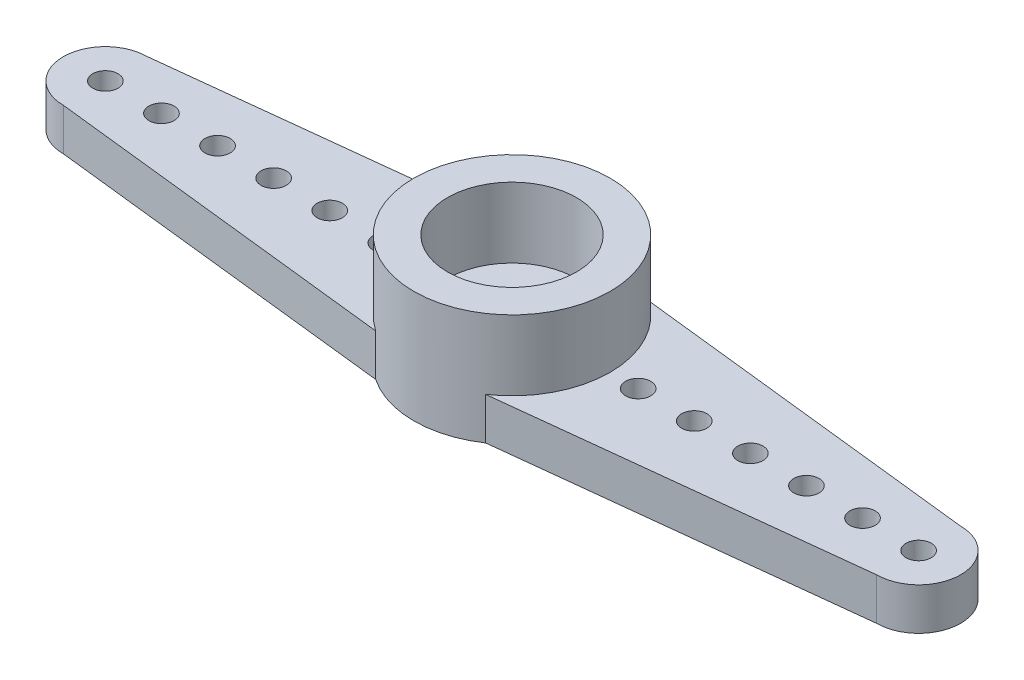
SolidWorks part; units mm, degrees
ref_plane "Front Plane" through (0, 0, 0) normal (0, 0, 1) x (1, 0, 0)
ref_plane "Top Plane" through (0, 0, 0) normal (0, 1, 0) x (1, 0, 0)
ref_plane "Right Plane" through (0, 0, 0) normal (1, 0, 0) x (0, 0, -1)
sketch "Sketch1" plane through (0, 0, 0) normal (0, 1, 0) x (1, 0, 0)
  line L0 (-16, 0) -> (16, 0) construction
  line L1 (0, 8.25) -> (0, -8.25) construction
  line L2 (-1.9596, 2.9) -> (-14.5, 1.5)
  line L3 (-1.9596, -2.9) -> (-14.5, -1.5)
  line L4 (1.9596, 2.9) -> (14.5, 1.5)
  line L5 (1.9596, -2.9) -> (14.5, -1.5)
  circle A0 centre (-14.5, 0) radius 0.45
  circle A1 centre (-12.5, 0) radius 0.45
  circle A2 centre (-10.5, 0) radius 0.45
  circle A3 centre (-8.5, 0) radius 0.45
  circle A4 centre (-6.5, 0) radius 0.45
  circle A5 centre (-4.5, 0) radius 0.45
  circle A7 centre (0, 0) radius 3.5
  circle A8 centre (0, 0) radius 2.3
  circle A9 centre (0, 0) radius 1.2
  arc A10 (-14.5, 1.5) -> (-14.5, -1.5) centre (-14.5, 0) ccw
  arc A11 (14.5, 1.5) -> (14.5, -1.5) centre (14.5, 0) cw
  circle A12 centre (4.5, 0) radius 0.45
  circle A13 centre (6.5, 0) radius 0.45
  circle A14 centre (8.5, 0) radius 0.45
  circle A15 centre (10.5, 0) radius 0.45
  circle A16 centre (12.5, 0) radius 0.45
  circle A17 centre (14.5, 0) radius 0.45
  point P3 (0, 0)
  point P6 (0, 0)
  point P27 (0, 3.5)
  point P29 (0, 0)
  point P30 (-17.2598, -0.1412)
  point P31 (-13.5328, 0)
  point P49 (0, 0)
  dimension "D3" = 2
  dimension "D4" = 2
  dimension "D9" = 1.5
  dimension "D10" = 0.9
  dimension "D2" = 7
  dimension "D11" = 2.4
  dimension "D13" = 1.5
  dimension "D1" = 32
  dimension "D5" = 2
  dimension "D6" = 2
  dimension "D7" = 2
  dimension "D8" = 1.2
  dimension "D12" = 0.6
extrude "Boss-Extrude1" add sketch "Sketch1" along normal blind 1.5 contours L2 A10 L3 A7 A0 A1 A2 A3 A4 A5 | A11 L4 A7 L5 A16 A14 A12 A13 A15 A17 | A7 A8 | A8 A9 region at (-3.6519, 0, 0) region at (0, 0, -3.401) region at (8.2129, 0, -2.049) region at (-2.2349, 0, 0)
extrude "Boss-Extrude2" add sketch "Sketch1<4>" along normal blind 2.5 from surface contours A7 A8 region at (0, 0, -3.401) starting at face at (-14.5, 1.5, 0.45)
sketch "Sketch1<4>" plane through (0, 0, 0) normal (0, 1, 0) x (1, 0, 0) same geometry as "Sketch1"
extrude "Cut-Extrude1" cut sketch "Sketch1<5>" along normal blind 0.5 contours A8 A9 region at (-2.2349, 0, 0)
sketch "Sketch1<5>" plane through (0, 0, 0) normal (0, 1, 0) x (1, 0, 0) same geometry as "Sketch1"
